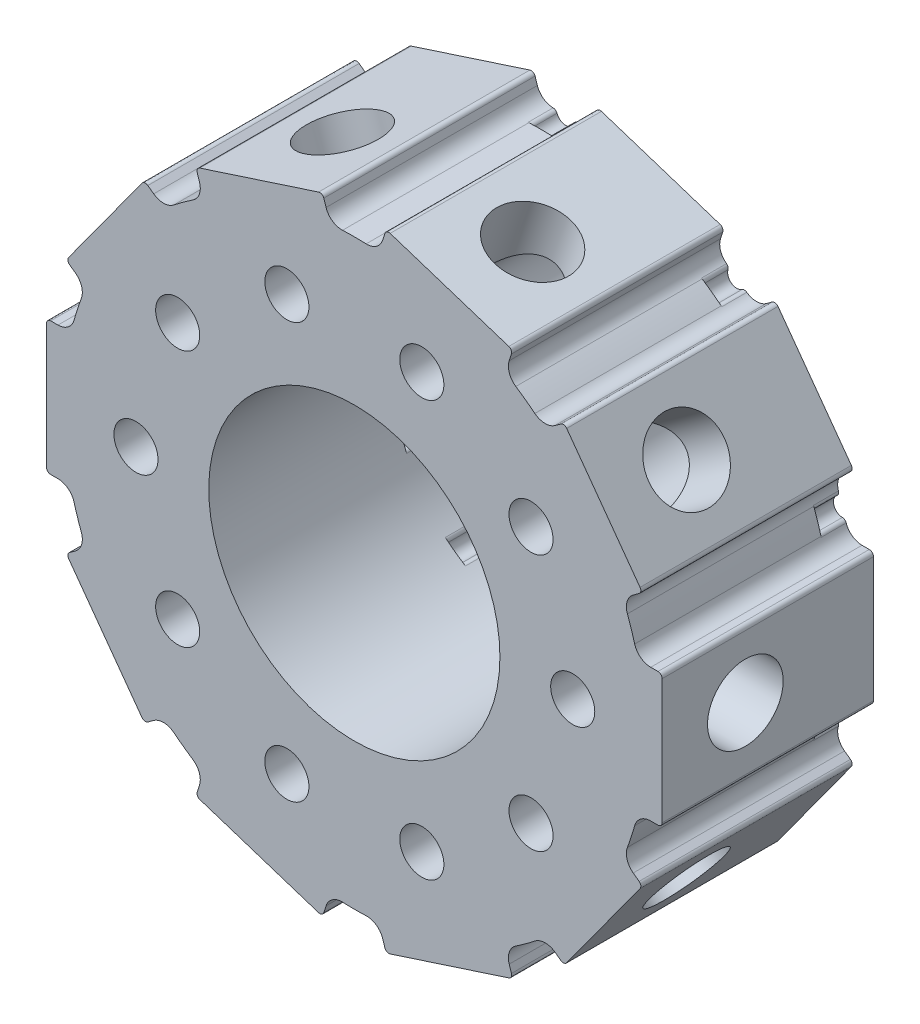
SolidWorks part; units mm, degrees
material "Polyetheretherketone (PEEK)"
ref_plane "Front Plane" through (0, 0, 0) normal (0, 0, 1) x (1, 0, 0)
ref_plane "Top Plane" through (0, 0, 0) normal (0, 1, 0) x (1, 0, 0)
ref_plane "Right Plane" through (0, 0, 0) normal (1, 0, 0) x (0, 0, -1)
sketch "Sketch1" plane through (0, 0, 0) normal (0, 0, 1) x (1, 0, 0)
  circle A0 centre (0, 0) radius 35
  circle A1 centre (0, 0) radius 17.5
  dimension "D1" = 35
  dimension "D2" = 70
extrude "Boss-Extrude1" add sketch "Sketch1" along normal blind 25.4
ref_axis "Axis1" through (0, 0, -1) along (0, 0, 1)
hole_wizard "M5 Clearance Hole1" positions "Sketch2" profile "Sketch3" hole size "M5" standard "ANSI Metric" end condition through all
sketch "Sketch2" plane through (0, 0, 25.4) normal (0, 0, 1) x (1, 0, 0)
  point P0 (26.25, 0)
  dimension "D1" = 26.25
sketch "Sketch3" plane through (26.25, 0, 25.4) normal (1, 0, 0) x (0, -1, 0)
  line L0 (0, 0) -> (0, 25.4)
  line L1 (0, 25.4) -> (2.65, 25.4)
  line L2 (2.65, 25.4) -> (2.65, 0)
  line L5 (2.65, 0) -> (0, 0)
  line L11 (0, -6.35) -> (0, 107.95) construction
  dimension "Thru Hole Dia." = 5.3
  dimension "Thru Hole Depth" = 25.4
ref_plane "Plane1" through (35, 0, 0) normal (1, 0, 0) x (0, 0, -1)
ref_plane "Plane2" through (37, 0, 0) normal (1, 0, 0) x (0, 0, -1)
sketch "Sketch8" plane through (37, 0, 0) normal (1, 0, 0) x (0, 0, -1)
  line L1 (-25.4, 35) -> (-25.4, -35) construction
  line L2 (-25.4, 8) -> (0, 8)
  line L3 (-25.4, 8) -> (-25.4, -8)
  line L4 (-25.4, -8) -> (0, -8)
  line L5 (0, 8) -> (0, -8)
  line L6 (1, 0) -> (-21, 0) construction
  line L7 (0, -35) -> (0, 35) construction
  circle A0 centre (-15.4, 0) radius 7.5 construction
  dimension "D1" = 15
  dimension "D2" = 10
  dimension "D3" = 8
  dimension "D4" = 8
extrude "Boss-Extrude2" add sketch "Sketch8" against normal up to surface (2.9265 mm away) up to face at (35, 0, 25.4)
fillet "Fillet3" radius 2 2 edges at (34.0735, -8, 12.7) (34.0735, 8, 12.7)
fillet "Fillet4" radius 0.5 2 edges at (37, 8, 12.7) (37, -8, 12.7)
hole_wizard "1/8-27 NPSM Tapped Hole1" positions "Sketch10" profile "Sketch11" tap size "1/8-27 NPSM" standard "ANSI Inch"
sketch "Sketch10" plane through (37, 0, 0) normal (1, 0, 0) x (0, 0, -1)
  line L0 (-25.4, 7.5) -> (-25.4, -7.5) construction
  line L1 (0, 8) -> (-25.4, 8) construction
  point P0 (-15.4, 0)
  dimension "D1" = 10
  dimension "D2" = 8
sketch "Sketch11" plane through (37, 0, 15.4) normal (0, 1, 0) x (0, 0, -1)
  line L0 (0, 0) -> (0, 12.7319)
  line L1 (0, 12.7319) -> (4.5466, 10)
  line L2 (4.5466, 10) -> (4.5466, 0)
  line L5 (4.5466, 0) -> (0, 0)
  line L10 (0, 12.7319) -> (-4.5466, 10) construction
  line L11 (0, -6.35) -> (0, 107.95) construction
  dimension "Tap Drill Dia." = 9.0932
  dimension "Tap Drill Depth" = 10
  dimension "Drill Angle" = 118
cosmetic thread "Hole Thread3" parameters "D1"=9.96, "D2"=10.0838
hole_wizard "Ø10.0mm Dowel Hole1" positions "Sketch6" profile "Sketch7" hole size "Ø10.0" standard "ANSI Metric"
sketch "Sketch6" plane through (0, 0, 0) normal (0, 0, -1) x (-1, 0, 0)
  circle A1 centre (-26.25, 0) radius 2.65 construction
  point P0 (-26.25, 0)
sketch "Sketch7" plane through (26.25, 0, 0) normal (1, 0, 0) x (0, 1, 0)
  line L0 (0, 0) -> (0, 21.0043)
  line L1 (0, 21.0043) -> (5, 18)
  line L2 (5, 18) -> (5, 0)
  line L5 (5, 0) -> (0, 0)
  line L10 (0, 21.0043) -> (-5, 18) construction
  line L11 (0, -6.35) -> (0, 107.95) construction
  dimension "Hole Dia." = 10
  dimension "Hole Depth" = 18
  dimension "Drill Angle" = 118
pattern_circular "CirPattern3" count 10 every 36 about axis through (0, 0, -1) along (0, 0, 1) of "Ø10.0mm Dowel Hole1", "1/8-27 NPSM Tapped Hole1", "Boss-Extrude2", "M5 Clearance Hole1", "Fillet3", "Fillet4"
sketch "Sketch9" plane through (0, 0, 0) normal (0, 0, 1) x (1, 0, 0)
  line L0 (0, 0) -> (37.432, 0) construction
  line L1 (0, 0) -> (34.5516, 11.2265) construction
  circle A0 centre (16.6435, 5.4078) radius 1.1
  circle A1 centre (33.287, 10.8156) radius 1.1
  circle A2 centre (0, 0) radius 35 construction
  circle A3 centre (0, 0) radius 17.5 construction
  dimension "D1" = 2.2
  dimension "D2" = 2.2
  dimension "D3" = 18
extrude "Cut-Extrude2" cut sketch "Sketch9" along normal blind 3
pattern_circular "CirPattern2" count 10 every 36 about axis through (0, 0, -1) along (0, 0, 1) of "Cut-Extrude2"
fillet "Fillet1" radius 0.5 40 edges at (9.3764, 14.7761, 1.5) (11.1554, 13.4836, 1.5) (-1.0995, 17.4654, 1.5) (1.0995, 17.4654, 1.5) (-11.1554, 13.4836, 1.5) (-9.3764, 14.7761, 1.5) (-16.9504, 4.3515, 1.5) (-16.2709, 6.4428, 1.5) (-16.2709, -6.4428, 1.5) (-16.9504, -4.3515, 1.5) (-9.3764, -14.7761, 1.5) (-11.1554, -13.4836, 1.5) (1.0995, -17.4654, 1.5) (-1.0995, -17.4654, 1.5) (16.2709, 6.4428, 1.5) (16.9504, 4.3515, 1.5) (11.1554, -13.4836, 1.5) (9.3764, -14.7761, 1.5) (16.9504, -4.3515, 1.5) (16.2709, -6.4428, 1.5) (19.6725, -28.9481, 1.5) (21.4521, -27.6551, 1.5) (-1.0999, -34.9827, 1.5) (1.0999, -34.9827, 1.5) (-21.4521, -27.6551, 1.5) (-19.6725, -28.9481, 1.5) (-33.6104, -9.7642, 1.5) (-32.9307, -11.8563, 1.5) (-32.9307, 11.8563, 1.5) (-33.6104, 9.7642, 1.5) (-19.6725, 28.9481, 1.5) (-21.4521, 27.6551, 1.5) (1.0999, 34.9827, 1.5) (-1.0999, 34.9827, 1.5) (21.4521, 27.6551, 1.5) (19.6725, 28.9481, 1.5) (33.6104, 9.7642, 1.5) (32.9307, 11.8563, 1.5) (32.9307, -11.8563, 1.5) (33.6104, -9.7642, 1.5)
sketch "Sketch13" plane through (0, 0, 25.4) normal (0, 0, 1) x (1, 0, 0)
  circle A0 centre (0, 0) radius 12.5
  dimension "D1" = 25
extrude "Boss-Extrude3" [suppressed] add sketch "Sketch13" against normal blind 25.4 separate body
sketch "Sketch14" [suppressed] plane through (0, 0, 25.4) normal (0, 0, 1) x (1, 0, 0)
  line L0 (1.5, -19.7267) -> (1.5, -1.5)
  line L1 (-19.6825, 1.5) -> (21.2748, 1.5) construction
  line L2 (-19.6825, 1.5) -> (-19.6825, -1.5)
  line L3 (-19.6825, -1.5) -> (21.2748, -1.5) construction
  line L4 (21.2748, 1.5) -> (21.2748, -1.5)
  line L5 (-1.5, 20.4344) -> (1.5, 20.4344)
  line L6 (-1.5, 20.4344) -> (-1.5, -19.7267) construction
  line L7 (-1.5, -19.7267) -> (1.5, -19.7267)
  line L8 (1.5, 20.4344) -> (1.5, -19.7267) construction
  line L9 (1.5, -1.5) -> (21.2748, -1.5)
  line L10 (21.2748, 1.5) -> (1.5, 1.5)
  line L11 (1.5, 1.5) -> (1.5, 20.4344)
  line L12 (-1.5, 20.4344) -> (-1.5, 1.5)
  line L13 (-1.5, 1.5) -> (-19.6825, 1.5)
  line L14 (-19.6825, -1.5) -> (-1.5, -1.5)
  line L15 (-1.5, -1.5) -> (-1.5, -19.7267)
  dimension "D1" = 1.5
  dimension "D2" = 1.5
  dimension "D3" = 1.5
  dimension "D4" = 1.5
extrude "Boss-Extrude4" [suppressed] add sketch "Sketch14" against normal blind 3
fillet "Fillet5" [suppressed] radius 2
